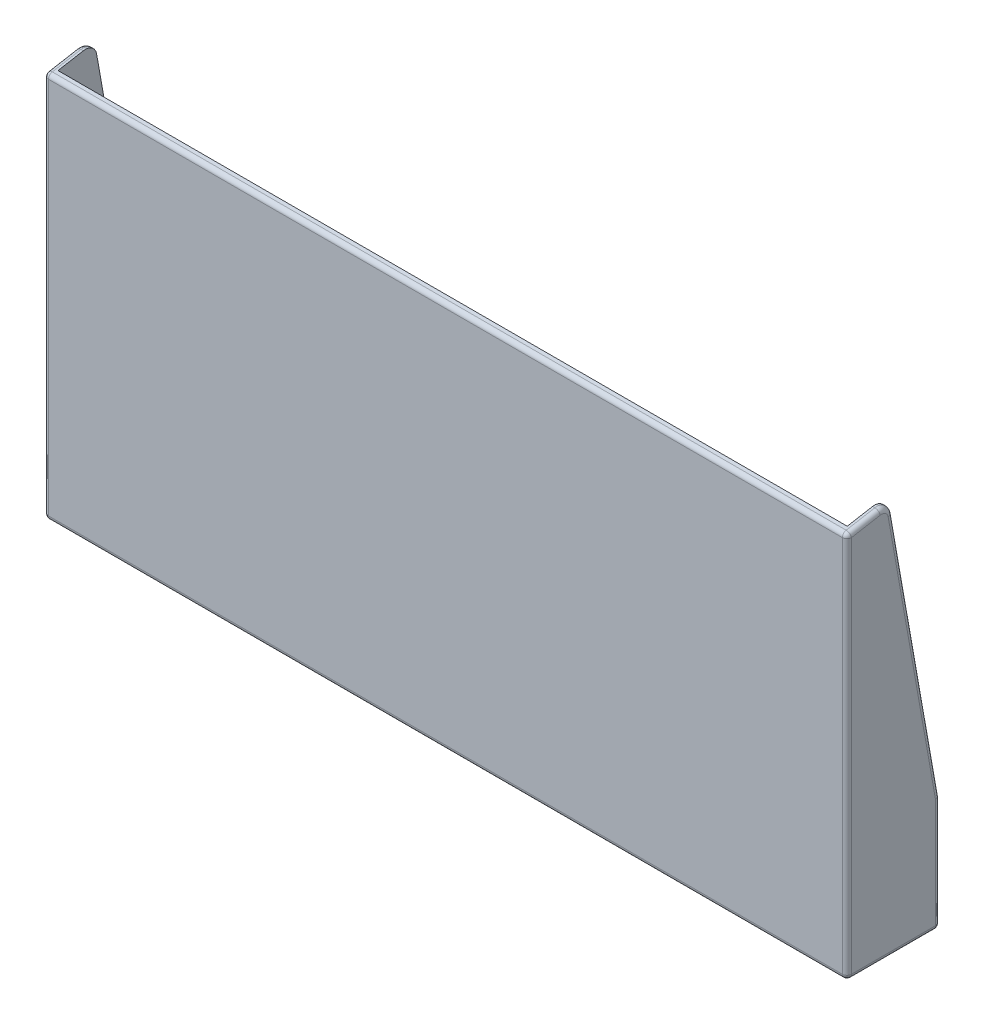
SolidWorks part; units mm, degrees
ref_plane "Front Plane" through (0, 0, 0) normal (0, 0, 1) x (1, 0, 0)
ref_plane "Top Plane" through (0, 0, 0) normal (0, 1, 0) x (1, 0, 0)
ref_plane "Right Plane" through (0, 0, 0) normal (1, 0, 0) x (0, 0, -1)
sketch "bottomplate" plane through (231.685, 0, 0) normal (1, 0, 0) x (0, 0, -1)
  line L0 (0, -72.0932) -> (-3.1401, -72.0932)
  line L1 (-3.1401, -72.0932) -> (-3.1401, 96.6415)
  line L2 (0, 97.1952) -> (11.0516, 99.1439) construction
  line L3 (-3.1401, 96.6415) -> (0, 97.1952)
  line L4 (0, 97.1952) -> (0, -72.0932)
  dimension "D1" = 0
extrude "B" add sketch "bottomplate" against normal up to surface (344.5411 mm away)
sketch "leftside" plane through (-112.8561, 0, 0) normal (-1, 0, 0) x (0, 0, 1)
  line L0 (3.1401, -72.0932) -> (-35.5061, -72.0932)
  line L2 (-37.5061, -70.0932) -> (-37.5061, -22.0932)
  line L3 (-37.5061, -22.0932) -> (-16.8439, 95.0881)
  line L5 (-11.0516, 99.1439) -> (3.1401, 96.6415)
  line L6 (3.1401, 96.6415) -> (3.1401, -72.0932)
  arc A0 (-35.5061, -72.0932) -> (-37.5061, -70.0932) centre (-35.5061, -70.0932) cw
  arc A1 (-11.0516, 99.1439) -> (-16.8439, 95.0881) centre (-11.9198, 94.2199) ccw
extrude "L" add sketch "leftside" along normal blind 3
sketch "rightside" plane through (231.685, 0, 0) normal (1, 0, 0) x (0, 0, -1)
  line L0 (-3.1401, -72.0932) -> (35.5061, -72.0932)
  line L2 (37.5061, -70.0932) -> (37.5061, -22.0932)
  line L3 (37.5061, -22.0932) -> (16.8439, 95.0881)
  line L5 (11.0516, 99.1439) -> (-3.1401, 96.6415)
  line L6 (-3.1401, 96.6415) -> (-3.1401, -72.0932)
  arc A0 (35.5061, -72.0932) -> (37.5061, -70.0932) centre (35.5061, -70.0932) ccw
  arc A1 (16.8439, 95.0881) -> (11.0516, 99.1439) centre (11.9198, 94.2199) ccw
extrude "R" add sketch "rightside" along normal blind 3
fillet "Fillet1" radius 2 2 edges at (59.4145, -72.0932, 3.1401) (59.4145, 96.6415, 3.1401)
fillet "Fillet2" radius 2 18 edges at (234.685, 36.4975, -27.175) (234.685, 98.3156, -14.7877) (234.685, 98.0384, -4.7821) (234.685, 96.2489, 2.6722) (234.685, -46.0932, -37.5061) (234.685, -71.5074, -36.9203) (234.685, -72.0932, -17.183) (234.685, -71.5074, 2.5543) (-115.8561, -46.0932, -37.5061) (-115.8561, -71.5074, -36.9203) (-115.8561, -72.0932, -17.183) (-115.8561, -71.5074, 2.5543) (-115.8561, 36.4975, -27.175) (-115.8561, 98.3156, -14.7877) (-115.8561, 98.0384, -4.7821) (-115.8561, 96.2489, 2.6722) (234.685, 12.4351, 3.1401) (-115.8561, 12.4351, 3.1401)
